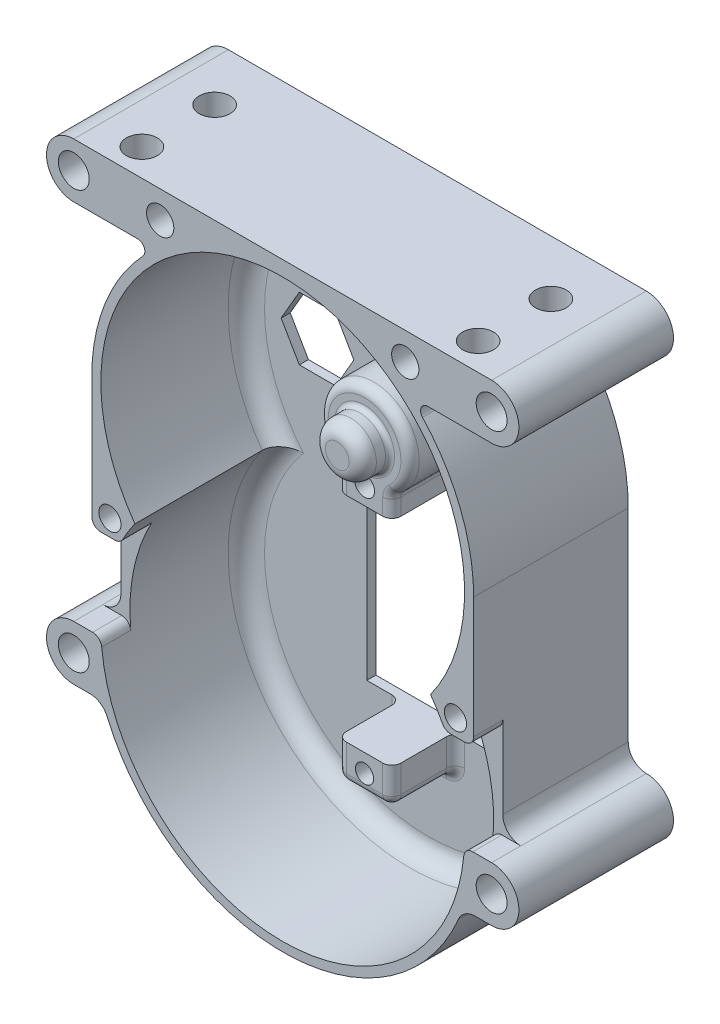
SolidWorks part; units mm, degrees
ref_plane "Ebene vorne" through (0, 0, 0) normal (0, 0, 1) x (1, 0, 0)
ref_plane "Ebene oben" through (0, 0, 0) normal (0, 1, 0) x (1, 0, 0)
ref_plane "Ebene rechts" through (0, 0, 0) normal (1, 0, 0) x (0, 0, -1)
sketch "groundplate" plane through (0, 0, 0) normal (0, 0, 1) x (1, 0, 0)
  line L0 (1, 5.6926) -> (1, -17.6074) construction
  line L1 (22, 5.6926) -> (22, -17.6074) construction
  line L2 (-20, 5.6926) -> (-20, -17.6074) construction
  line L3 (22, 5.6926) -> (22, -17.6074)
  line L4 (-20, 5.6926) -> (-20, -17.6074)
  arc A0 (-20, 5.6926) -> (22, 5.6926) centre (1, 5.6926) cw
  arc A1 (-20, -17.6074) -> (22, -17.6074) centre (1, -17.6074) ccw
  dimension "D1" = 23.3
  dimension "D2" = 42
  dimension "D3" = 23.3
extrude "body" add sketch "groundplate" along normal blind 17 contours L4 A1 A0 region at (1, -5.9574, 0)
sketch "main-box" plane through (0, 0, 17) normal (0, 0, 1) x (1, 0, 0)
  line L0 (-20, 5.6926) -> (22, 5.6926) construction
  line L1 (-20, -17.6074) -> (22, -17.6074) construction
  arc A0 (-20, -17.6074) -> (22, -17.6074) centre (1, -17.6074) ccw construction
  circle A1 centre (1, 5.6926) radius 20
  circle A2 centre (1, -17.6074) radius 20
  dimension "D1" = 40
extrude "box" cut sketch "main-box" against normal blind 16 contours A1 A2 | A2 A1 | A1 A2 region at (1, 10.7505, 17) region at (1, -5.9574, 17) region at (1, -22.6654, 17)
sketch "rack-channel" plane through (0, 0, 17) normal (0, 0, 1) x (1, 0, 0)
  line L0 (-20, -17.6074) -> (22, -17.6074) construction
  line L1 (-20, 5.6926) -> (-20, -17.6074) construction
  line L2 (-20, -8.6074) -> (22, -8.6074)
  line L3 (-20, -8.6074) -> (-20, -18.6074)
  line L4 (-20, -18.6074) -> (22, -18.6074)
  line L5 (22, -8.6074) -> (22, -18.6074)
  dimension "D1" = 1
  dimension "D2" = 10
extrude "rack-ch" cut sketch "rack-channel" against normal blind 3.2
ref_axis "Achse1" through (1, 5.6926, 1) along (0, 0, 1)
ref_axis "Achse2" through (1, -17.6074, 1) along (0, 0, 1)
fillet "Verrundung1" radius 1 2 edges at (22, -8.6074, 15.4) (-20, -8.6074, 15.4)
sketch "wings-" plane through (0, 0, 17) normal (0, 0, 1) x (1, 0, 0)
  line L0 (-36.7847, -18.6074) -> (40.263, -18.6074) construction
  line L1 (-36.7847, -24.6074) -> (40.263, -24.6074) construction
  line L2 (-19.9762, -18.6074) -> (-21.9762, -18.6074)
  line L3 (-18.799, -24.6074) -> (-21.9762, -24.6074)
  line L4 (-21.9762, -18.6074) -> (-21.9762, -24.6074) construction
  line L5 (-19, -17.6074) -> (21, -17.6074) construction
  line L6 (21.9762, -18.6074) -> (23.9762, -18.6074)
  line L7 (23.9762, -18.6074) -> (23.9762, -24.6074) construction
  line L8 (20.799, -24.6074) -> (23.9762, -24.6074)
  arc A0 (-21.9762, -18.6074) -> (-21.9762, -24.6074) centre (-21.9762, -21.6074) ccw
  arc A1 (-15.2566, -5.9574) -> (17.2566, -5.9574) centre (1, -17.6074) ccw construction
  arc A2 (-16.8606, -8.6074) -> (-18.975, -18.6074) centre (1, -17.6074) ccw construction
  arc A3 (-19.9762, -18.6074) -> (-18.799, -24.6074) centre (1, -17.6074) ccw
  arc A4 (-19.9762, -18.6074) -> (21.9762, -18.6074) centre (1, -17.6074) ccw construction
  arc A5 (23.9762, -18.6074) -> (23.9762, -24.6074) centre (23.9762, -21.6074) cw
  arc A6 (21.9762, -18.6074) -> (20.799, -24.6074) centre (1, -17.6074) cw
  dimension "D3" = 2
  dimension "D1" = 6
  dimension "D2" = 2
extrude "wings" add sketch "wings-" against normal blind 17
sketch "Skizze6" plane through (0, 0, 17) normal (0, 0, 1) x (1, 0, 0)
  circle A0 centre (-21.9762, -21.6074) radius 1.7
  circle A1 centre (23.9762, -21.6074) radius 1.7
  dimension "D1" = 3.4
extrude "wing-hole" cut sketch "Skizze6" against normal through all
fillet "Verrundung2" radius 2 2 edges at (20.799, -24.6074, 8.5) (-18.799, -24.6074, 8.5)
fillet "Verrundung3" radius 2 2 edges at (21.9762, -18.6074, 6.9) (-19.9762, -18.6074, 6.9)
sketch "servo-cut" plane through (0, 0, 1) normal (0, 0, 1) x (1, 0, 0)
  line L0 (-32.3558, -24.1074) -> (45.0227, -24.1074) construction
  line L1 (45.0227, -24.1074) -> (1, -24.1074) construction
  line L2 (1, 26.6926) -> (1, -38.6074) construction
  line L4 (-5.75, -0.6074) -> (7.75, -0.6074)
  line L5 (-5.75, -0.6074) -> (-5.75, -24.1074)
  line L6 (-5.75, -24.1074) -> (7.75, -24.1074)
  line L7 (7.75, -0.6074) -> (7.75, -24.1074)
  line L8 (-5.75, -0.6074) -> (7.75, -24.1074) construction
  line L9 (-5.75, -24.1074) -> (7.75, -0.6074) construction
  arc A1 (-18.3255, -25.8248) -> (20.3255, -25.8248) centre (1, -17.6074) ccw construction
  point P12 (1, -12.3574)
  dimension "D1" = 6.5
  dimension "D2" = 23.5
  dimension "D3" = 13.5
extrude "servo-hole" cut sketch "servo-cut" against normal through all
sketch "Skizze8" plane through (0, 0, 1) normal (0, 0, 1) x (1, 0, 0)
  line L0 (1, 26.6926) -> (1, -38.6074) construction
  line L1 (-5.75, -24.1074) -> (7.75, -24.1074) construction
  line L2 (-2, -28.1074) -> (4, -28.1074)
  line L3 (-2, -28.1074) -> (-2, -24.1074)
  line L4 (-2, -24.1074) -> (4, -24.1074)
  line L5 (4, -28.1074) -> (4, -24.1074)
  line L6 (-2, -28.1074) -> (4, -24.1074) construction
  line L7 (-2, -24.1074) -> (4, -28.1074) construction
  line L8 (7.75, -0.6074) -> (-5.75, -0.6074) construction
  line L9 (-2, 3.3926) -> (4, 3.3926)
  line L10 (-2, 3.3926) -> (-2, -0.6074)
  line L11 (-2, -0.6074) -> (4, -0.6074)
  line L12 (4, 3.3926) -> (4, -0.6074)
  line L13 (-2, 3.3926) -> (4, -0.6074) construction
  line L14 (-2, -0.6074) -> (4, 3.3926) construction
  arc A1 (-18.3255, -25.8248) -> (20.3255, -25.8248) centre (1, -17.6074) ccw construction
  point P8 (1, -26.1074)
  point P15 (1, 1.3926)
  dimension "D1" = 6
  dimension "D2" = 4
  dimension "D3" = 4
  dimension "D4" = 6
extrude "servo-bore" add sketch "Skizze8" along normal blind 7
sketch "Skizze10" plane through (0, 0, 1) normal (0, 0, 1) x (1, 0, 0)
  circle A0 centre (1, 5.6926) radius 5
  dimension "D1" = 10
extrude "gear-holder" add sketch "Skizze10" along normal blind 7
sketch "main-gear-axis" plane through (0, 0, 8) normal (0, 0, 1) x (1, 0, 0)
  circle A0 centre (1, 5.6926) radius 2.8
  dimension "D1" = 5.6
extrude "axis" add sketch "main-gear-axis" along normal blind 3
fillet "Verrundung11" radius 1.5 1 edges at (3.8, 5.6926, 11)
fillet "Verrundung12" radius 0.5 1 edges at (3.8, 5.6926, 8)
fillet "Verrundung13" radius 1 2 edges at (-2, 1.6926, 4.5) (4, 1.6926, 4.5)
sketch "screw-hole" plane through (0, 0, 8) normal (0, 0, 1) x (1, 0, 0)
  line L0 (4, -26.1074) -> (-2, -26.1074) construction
  line L1 (4, -28.1074) -> (4, -24.1074) construction
  line L2 (-2, -24.1074) -> (-2, -28.1074) construction
  line L3 (-2, 0.3065) -> (4, 0.3065) construction
  line L4 (-2, 1.2204) -> (-2, -0.6074) construction
  line L5 (4, -0.6074) -> (4, 1.2204) construction
  circle A0 centre (1, -26.1074) radius 1
  circle A1 centre (1, 1.3065) radius 1.1
  dimension "D1" = 2
  dimension "D2" = 1
  dimension "D3" = 2.2
extrude "servo-holder-hole" cut sketch "screw-hole" against normal through all
fillet "Verrundung14" radius 1 10 edges at (4, 0.3065, 8) (4.0871, 1.6287, 8) (-2, 0.3065, 8) (-2.0871, 1.6287, 8) (4, 0.3065, 1) (4.0871, 1.6287, 1) (-2, 0.3065, 1) (-2.0871, 1.6287, 1) (1, 10.6926, 8) (1, 10.6926, 1)
fillet "Verrundung17" radius 1 8 edges at (1, -28.1074, 1) (-2, -26.1074, 8) (-2, -26.1074, 1) (4, -26.1074, 1) (4, -26.1074, 8) (1, -28.1074, 8) (4, -28.1074, 4.5) (-2, -28.1074, 4.5)
fillet "Verrundung18" radius 2 2 edges at (1, -37.6074, 1) (1, 25.6926, 1)
fillet "Verrundung19" radius 1 2 edges at (-16.8606, -8.6074, 15.4) (18.8606, -8.6074, 15.4)
fillet "Verrundung20" radius 1 2 edges at (20.975, -18.6074, 15.4) (-18.975, -18.6074, 15.4)
sketch "Skizze11" plane through (0, 0, 17) normal (0, 0, 1) x (1, 0, 0)
  line L0 (1, 26.6926) -> (1, -38.6074) construction
  arc A1 (-18.3255, -25.8248) -> (20.3255, -25.8248) centre (1, -17.6074) ccw construction
sketch "Skizze12" plane through (0, 0, 1) normal (0, 0, 1) x (1, 0, 0)
  line L0 (-19, 5.6926) -> (21, 5.6926) construction
  line L2 (-7.1727, 5.6926) -> (-9.1727, 9.1567)
  line L3 (-9.1727, 9.1567) -> (-13.1727, 9.1567)
  line L4 (-13.1727, 9.1567) -> (-15.1727, 5.6926)
  line L5 (-15.1727, 5.6926) -> (-13.1727, 2.2285)
  line L6 (-13.1727, 2.2285) -> (-9.1727, 2.2285)
  line L7 (-9.1727, 2.2285) -> (-7.1727, 5.6926)
  circle A0 centre (-11.1727, 5.6926) radius 3.4641 construction
  arc A1 (17.2566, -5.9574) -> (-15.2566, -5.9574) centre (1, 5.6926) ccw construction
  arc A2 (17.2566, -5.9574) -> (-15.2566, -5.9574) centre (1, 5.6926) ccw construction
extrude "Schnitt-Linear austragen1" cut sketch "Skizze12" against normal through all
pattern_circular "Kreismuster1" count 4 over 180 about axis through (1, 5.6926, 17) along (0, 0, 1) of "Schnitt-Linear austragen1" reverse direction yes
sketch "Skizze13" plane through (0, 0, 17) normal (0, 0, 1) x (1, 0, 0)
  line L0 (-20, 5.6926) -> (22, 5.6926) construction
  line L1 (-20, 5.6926) -> (-20, -7.6074) construction
  line L2 (22, 5.6926) -> (22, -7.6074) construction
  circle A0 centre (-18, -6.8074) radius 1.2193
  circle A1 centre (20, -6.8074) radius 1.2193
  dimension "D1" = 2
  dimension "D3" = 2
  dimension "D2" = 12.5
extrude "Schnitt-Linear austragen2" cut sketch "Skizze13" against normal through all contours A1 | A0
sketch "base-wings" plane through (0, 0, 17) normal (0, 0, 1) x (1, 0, 0)
  line L0 (23.9762, 21.3426) -> (15.0028, 21.3426)
  line L1 (-21.9762, 21.3426) -> (-13.0028, 21.3426)
  line L2 (-21.9762, -21.6074) -> (-21.9762, 32.2683) construction
  line L3 (23.9762, -21.6074) -> (23.9762, 32.2683) construction
  line L4 (-21.9762, -21.6074) -> (23.9762, -21.6074) construction
  line L5 (-21.9762, 27.3426) -> (23.9762, 27.3426)
  line L7 (-21.9762, -21.6074) -> (23.9762, -21.6074) construction
  line L8 (-21.9762, -21.6074) -> (-21.9762, 24.3426) construction
  line L9 (-21.9762, 24.3426) -> (23.9762, 24.3426) construction
  line L10 (23.9762, -21.6074) -> (23.9762, 24.3426) construction
  arc A0 (-21.9762, 27.3426) -> (-21.9762, 21.3426) centre (-21.9762, 24.3426) ccw
  arc A1 (23.9762, 27.3426) -> (23.9762, 21.3426) centre (23.9762, 24.3426) cw
  circle A4 centre (-21.9762, 24.3426) radius 1.7
  circle A5 centre (23.9762, 24.3426) radius 1.7
  arc A6 (22, 5.6926) -> (-20, 5.6926) centre (1, 5.6926) ccw construction
  arc A7 (-13.0028, 21.3426) -> (15.0028, 21.3426) centre (1, 5.6926) cw
  arc M18 (22, 5.6926) -> (-20, 5.6926) centre (1, 5.6926) ccw
  dimension "D3" = 3.4
  dimension "D1" = 45.95
  dimension "D2" = 45.9524
extrude "base" add sketch "base-wings" against normal blind 17 contours A1 L5 A0 L1 L0 A5 A4 M18 region at (19.4895, 21.8655, 17)
sketch "Skizze15" plane through (0, 21.3426, 0) normal (0, -1, 0) x (1, 0, 0)
  line L0 (-17.4895, 0) -> (-17.4895, 17) construction
  line L1 (-21.9762, 0) -> (-13.0028, 0) construction
  line L2 (-21.9762, 17) -> (-13.0028, 17) construction
  line L3 (19.4895, 0) -> (19.4895, 17) construction
  line L4 (23.9762, 0) -> (15.0028, 0) construction
  line L5 (23.9762, 17) -> (15.0028, 17) construction
  circle A0 centre (-17.4895, 6) radius 1.7
  circle A1 centre (-17.4895, 14) radius 1.7
  circle A2 centre (19.4895, 14) radius 1.7
  circle A3 centre (19.4895, 6) radius 1.7
  dimension "D1" = 6
  dimension "D3" = 3.4
  dimension "D4" = 6
  dimension "D2" = 3
  dimension "D5" = 3
extrude "base-holes" cut sketch "Skizze15" against normal through all
fillet "Verrundung22" radius 0.8 2 edges at (-13.0028, 21.3426, 8.5) (15.0028, 21.3426, 8.5)
sketch "Skizze16" plane through (0, 0, 17) normal (0, 0, 1) x (1, 0, 0)
  line L0 (-24.9762, 24.3426) -> (26.9762, 24.3426) construction
  arc A0 (-21.9762, 27.3426) -> (-21.9762, 21.3426) centre (-21.9762, 24.3426) ccw construction
  arc A1 (23.9762, 21.3426) -> (23.9762, 27.3426) centre (23.9762, 24.3426) ccw construction
  circle A2 centre (14.4762, 24.3426) radius 1.5
  circle A5 centre (-12.4762, 24.3426) radius 1.5
  dimension "D1" = 3
  dimension "D3" = 12.5
  dimension "D5" = 12.5
extrude "Schnitt-Linear austragen4" cut sketch "Skizze16" against normal through all
